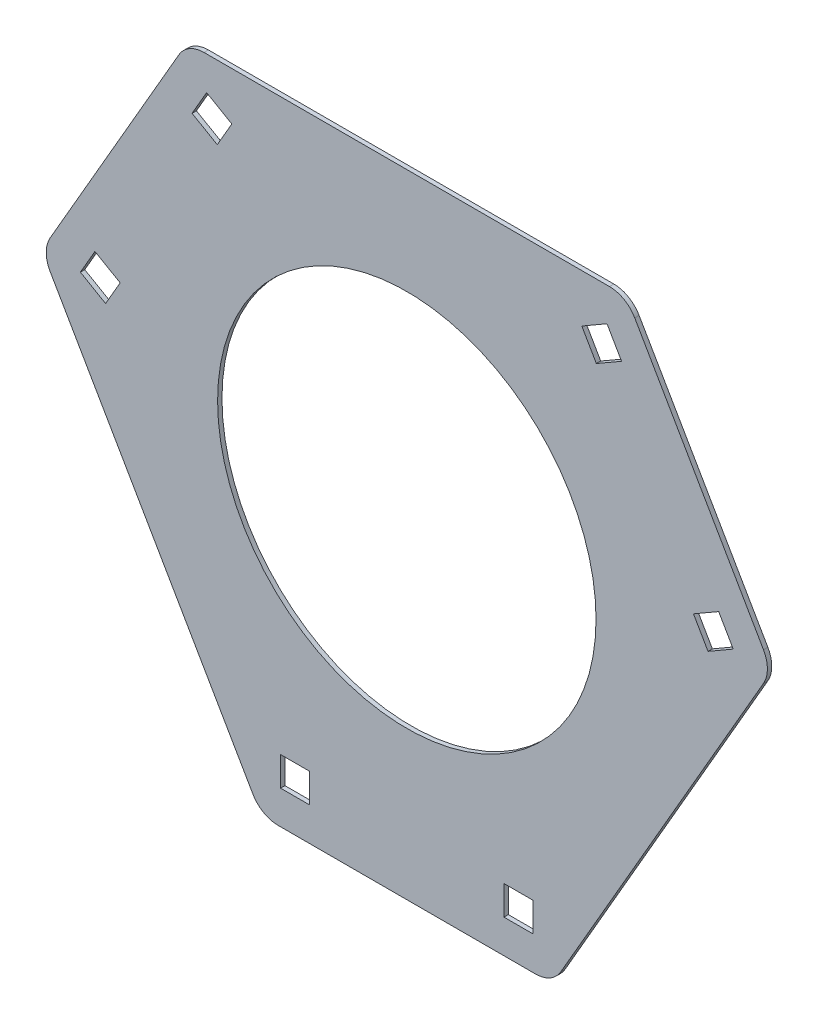
SolidWorks part; units mm, degrees
ref_plane "前视基准面" through (0, 0, 0) normal (0, 0, 1) x (1, 0, 0)
ref_plane "上视基准面" through (0, 0, 0) normal (0, 1, 0) x (1, 0, 0)
ref_plane "右视基准面" through (0, 0, 0) normal (1, 0, 0) x (0, 0, -1)
other "Configuration Table"
sketch "草图1" plane through (0, 0, 0) normal (0, 0, 1) x (1, 0, 0)
  line L0 (150.8203, 202.5462) -> (-150.8203, 202.5462)
  line L1 (-150.8203, 202.5462) -> (-250.8203, 29.3411)
  line L2 (-250.8203, 29.3411) -> (-100, -231.8873)
  line L3 (-100, -231.8873) -> (100, -231.8873)
  line L4 (100, -231.8873) -> (250.8203, 29.3411)
  line L5 (250.8203, 29.3411) -> (150.8203, 202.5462)
  line L6 (-200.8203, 115.9437) -> (175.4101, -101.2731) construction
  line L7 (0, 202.5462) -> (0, -231.8873) construction
  circle A0 centre (0, 0) radius 130
  point P7 (0, 0)
  point P12 (0, 0)
  point P13 (0, 0)
  point P18 (0, 0)
  point P70 (-122.2962, -44.0868)
  dimension "D7" = 120
  dimension "D3" = 260
  dimension "D1" = 120
  dimension "D2" = 120
  dimension "D4" = 120
  dimension "D5" = 120
  dimension "D6" = 200
extrude "凸台-拉伸1" add sketch "草图1" along normal blind 3 contours L4 L5 L0 L1 L2 L3 A0 | L5 L0 L1 L2 L3 L4 | A0 region at (195.0733, 112.6256, 0)
sketch "草图8" plane through (0, 0, 3) normal (0, 0, 1) x (1, 0, 0)
  line L0 (-137.5412, 179.5462) -> (-147.5412, 162.2257)
  line L1 (-137.5412, 179.5462) -> (-120.2207, 169.5462)
  line L2 (-147.5412, 162.2257) -> (-130.2207, 152.2257)
  line L3 (-120.2207, 169.5462) -> (-130.2207, 152.2257)
  line L4 (-150.8203, 202.5462) -> (-250.8203, 29.3411) construction
  line L5 (-214.2622, 46.6616) -> (-224.2622, 29.3411)
  line L6 (-214.2622, 46.6616) -> (-196.9417, 36.6616)
  line L7 (-224.2622, 29.3411) -> (-206.9417, 19.3411)
  line L8 (-196.9417, 36.6616) -> (-206.9417, 19.3411)
  line L9 (-86.7209, -208.8873) -> (-66.7209, -208.8873)
  line L10 (-86.7209, -208.8873) -> (-86.7209, -188.8873)
  line L11 (-66.7209, -208.8873) -> (-66.7209, -188.8873)
  line L12 (-86.7209, -188.8873) -> (-66.7209, -188.8873)
  line L13 (66.7209, -208.8873) -> (86.7209, -208.8873)
  line L14 (66.7209, -208.8873) -> (66.7209, -188.8873)
  line L15 (86.7209, -208.8873) -> (86.7209, -188.8873)
  line L16 (66.7209, -188.8873) -> (86.7209, -188.8873)
  line L17 (224.2622, 29.3411) -> (214.2622, 46.6616)
  line L18 (224.2622, 29.3411) -> (206.9417, 19.3411)
  line L19 (214.2622, 46.6616) -> (196.9417, 36.6616)
  line L20 (206.9417, 19.3411) -> (196.9417, 36.6616)
  line L21 (137.5412, 179.5462) -> (147.5412, 162.2257)
  line L22 (137.5412, 179.5462) -> (120.2207, 169.5462)
  line L23 (147.5412, 162.2257) -> (130.2207, 152.2257)
  line L24 (120.2207, 169.5462) -> (130.2207, 152.2257)
  line L25 (-150.8203, 202.5462) -> (-250.8203, 29.3411) construction
  line L26 (250.8203, 29.3411) -> (150.8203, 202.5462) construction
  line L27 (-100, -231.8873) -> (100, -231.8873) construction
  line L28 (-150.8203, 202.5462) -> (-50.8203, 29.3411) construction
  line L29 (-50.8203, 29.3411) -> (-250.8203, 29.3411) construction
  line L30 (150.8203, 202.5462) -> (50.8203, 29.3411) construction
  line L31 (50.8203, 29.3411) -> (250.8203, 29.3411) construction
  line L32 (-100, -231.8873) -> (0, -58.6822) construction
  line L33 (0, -58.6822) -> (100, -231.8873) construction
  dimension "D1" = 20
  dimension "D2" = 20
  dimension "D3" = 20
  dimension "D4" = 20
  dimension "D5" = 20
  dimension "D6" = 20
  dimension "D7" = 20
  dimension "D8" = 20
  dimension "D9" = 20
  dimension "D10" = 20
  dimension "D11" = 23
  dimension "D12" = 23
  dimension "D13" = 23
  dimension "D14" = 23
  dimension "D15" = 23
  dimension "D16" = 60
  dimension "D17" = 60
  dimension "D18" = 60
  dimension "D19" = 60
  dimension "D20" = 60
  dimension "D21" = 20
  dimension "D22" = 20
extrude "切除-拉伸4" cut sketch "草图8" against normal through all contours L0 L1 L3 L2 | L5 L6 L8 L7 | L21 L22 L24 L23 | L17 L18 L20 L19 | L9 L10 L12 L11 | L13 L14 L16 L15
fillet "圆角2" radius 20 6 edges at (100, -231.8873, 1.5) (-100, -231.8873, 1.5) (150.8203, 202.5462, 1.5) (250.8203, 29.3411, 1.5) (-250.8203, 29.3411, 1.5) (-150.8203, 202.5462, 1.5)
